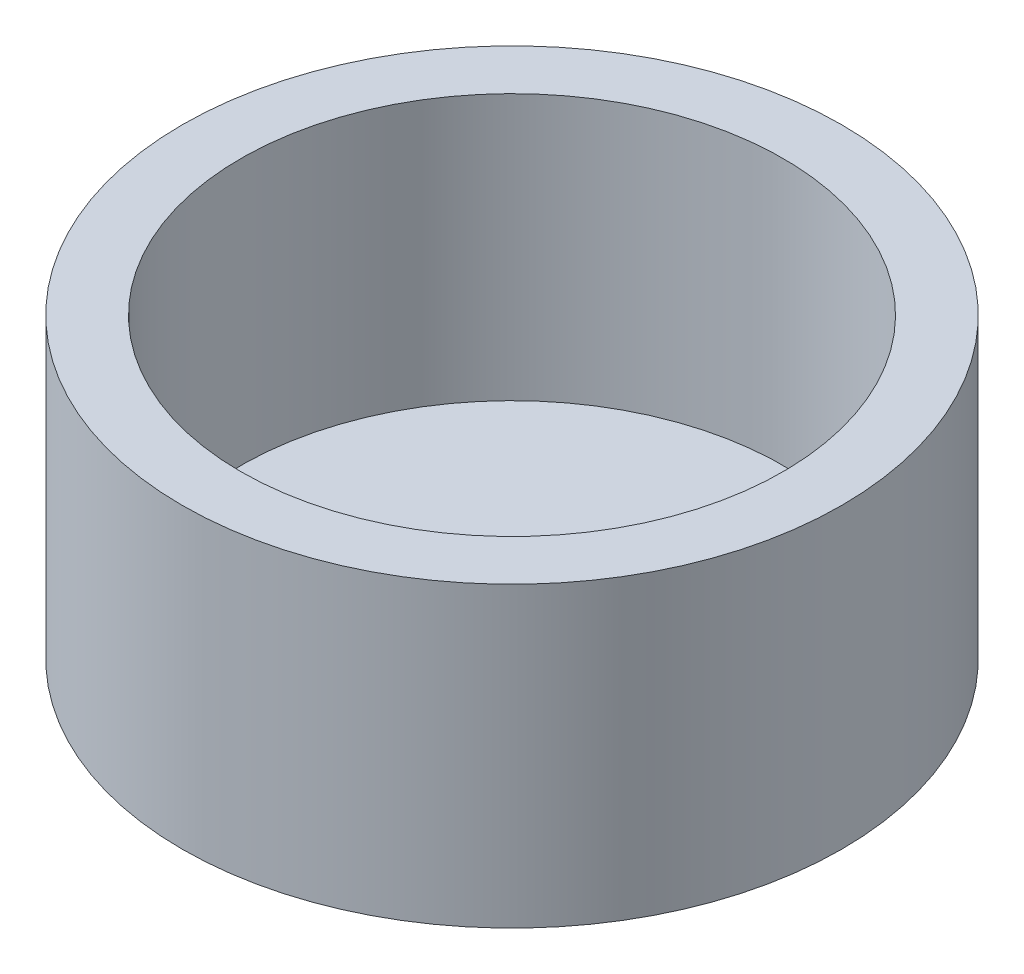
SolidWorks part; units mm, degrees
ref_plane "Front Plane" through (0, 0, 0) normal (0, 0, 1) x (1, 0, 0)
ref_plane "Top Plane" through (0, 0, 0) normal (0, 1, 0) x (1, 0, 0)
ref_plane "Right Plane" through (0, 0, 0) normal (1, 0, 0) x (0, 0, -1)
sketch "Sketch1" plane through (0, 0, 0) normal (0, 1, 0) x (1, 0, 0)
  circle A0 centre (0, 0) radius 31
  dimension "D1" = 62
extrude "Boss-Extrude1" add sketch "Sketch1" along normal blind 3
sketch "Sketch2" plane through (0, 3, 0) normal (0, 1, 0) x (1, 0, 0)
  circle A0 centre (0, 0) radius 25.5
  circle A1 centre (0, 0) radius 31
  circle A2 centre (0, 0) radius 31 construction
  dimension "D1" = 51
extrude "Boss-Extrude2" add sketch "Sketch2" along normal blind 25
sketch "Sketch4" plane through (0, 3, 0) normal (0, 1, 0) x (1, 0, 0)
  circle A0 centre (0, 0) radius 9
  dimension "D1" = 18
extrude "Cut-Extrude1" cut sketch "Sketch4" against normal through all
